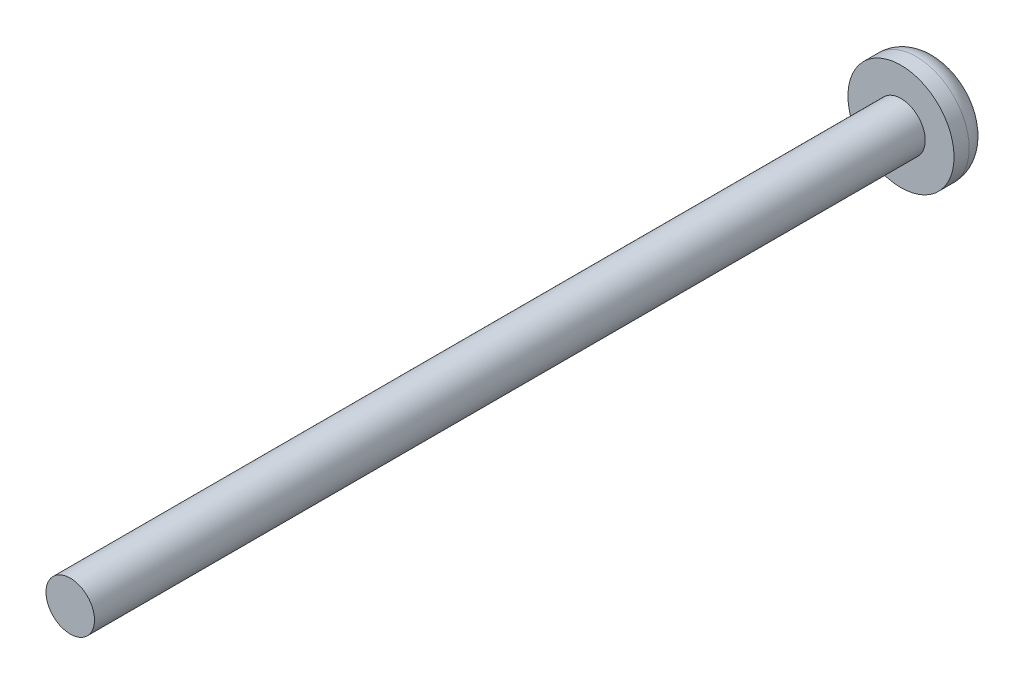
SolidWorks part; units mm, degrees
ref_plane "前基準面" through (0, 0, 0) normal (0, 0, 1) x (1, 0, 0)
ref_plane "上基準面" through (0, 0, 0) normal (0, 1, 0) x (1, 0, 0)
ref_plane "右基準面" through (0, 0, 0) normal (1, 0, 0) x (0, 0, -1)
sketch "草圖1" plane through (0, 0, 0) normal (0, 0, 1) x (1, 0, 0)
  circle A0 centre (0, 0) radius 1.75
  dimension "D1" = 3.5
extrude "伸長1" add sketch "草圖1" along normal blind 1.2
sketch "草圖2" plane through (0, 0, 1.2) normal (0, 0, 1) x (1, 0, 0)
  circle A0 centre (0, 0) radius 0.8
  dimension "D1" = 1.6
extrude "伸長2" add sketch "草圖2" along normal blind 27.4
sketch "草圖3" plane through (0, 0, 0) normal (0, 0, -1) x (-1, 0, 0)
  line L1 (-0.115, 1.2) -> (0.115, 1.2)
  line L2 (-0.115, 1.2) -> (-0.115, -1.2)
  line L3 (-0.115, -1.2) -> (0.115, -1.2)
  line L4 (0.115, 1.2) -> (0.115, -1.2)
  line L5 (-0.115, 1.2) -> (0.115, -1.2) construction
  line L6 (-0.115, -1.2) -> (0.115, 1.2) construction
  point P0 (0, 0)
  dimension "D1" = 2.4
  dimension "D2" = 0.23
sketch "草圖4" plane through (0, 0, 0) normal (1, 0, 0) x (0, 0, -1)
  line L0 (0, 0) -> (-0.85, 0) construction
  point P0 (-0.85, 0)
  dimension "D1" = 0.85
loft "除料-疊層拉伸1" cut profiles "草圖3", "草圖4"
pattern_circular "環狀複製排列1" count 4 over 360 about axis through (0, 0, 28.6) along (0, 0, -1) of "除料-疊層拉伸1"
fillet "圓角2" radius 0.7 1 edges at (1.75, 0, 0)
sketch "草圖5" plane through (0, 0, 28.6) normal (0, 0, 1) x (1, 0, 0)
  circle A0 centre (0, 0) radius 0.8 construction
  circle A1 centre (0, 0) radius 0.8
